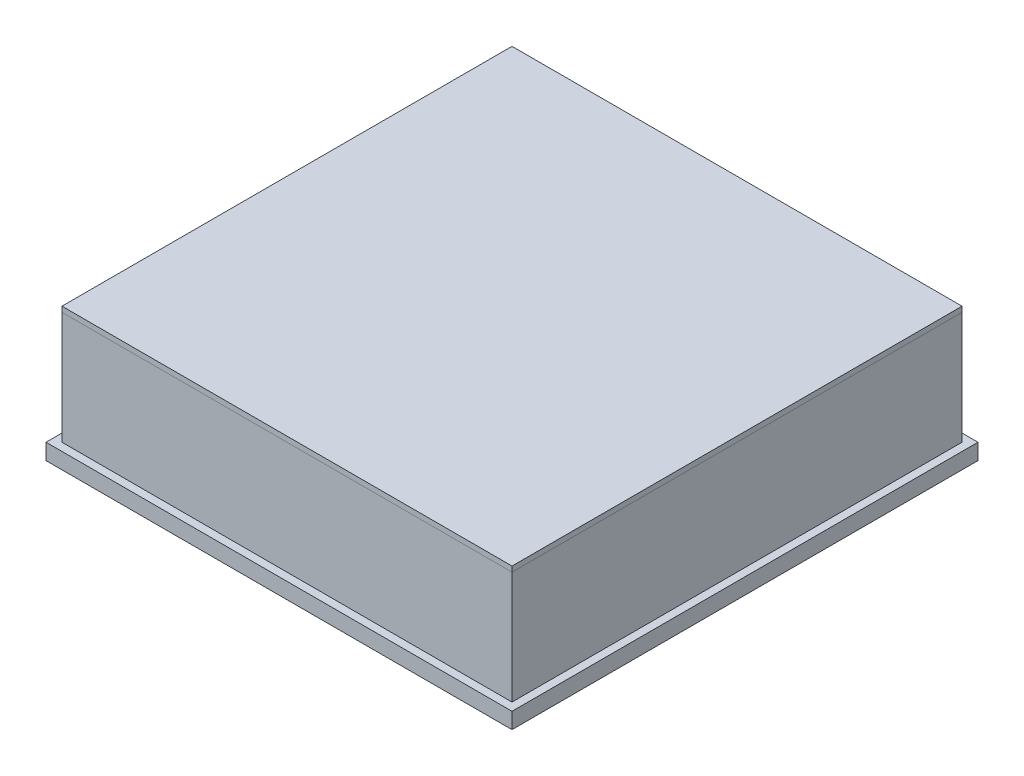
SolidWorks part; units mm, degrees
ref_plane "Front Plane" through (0, 0, 0) normal (0, 0, 1) x (1, 0, 0)
ref_plane "Top Plane" through (0, 0, 0) normal (0, 1, 0) x (1, 0, 0)
ref_plane "Right Plane" through (0, 0, 0) normal (1, 0, 0) x (0, 0, -1)
sketch "Sketch2" plane through (0, 0, 0) normal (0, 1, 0) x (1, 0, 0)
  line L0 (-4304.792, -4304.792) -> (-4304.792, 4304.792)
  line L1 (3999.992, -3999.992) -> (-3999.992, -3999.992)
  line L2 (3999.992, -3999.992) -> (3999.992, 3999.992)
  line L3 (3999.992, 3999.992) -> (-3999.992, 3999.992)
  line L4 (-3999.992, -3999.992) -> (-3999.992, 3999.992)
  line L5 (3999.992, -3999.992) -> (-3999.992, 3999.992) construction
  line L6 (3999.992, 3999.992) -> (-3999.992, -3999.992) construction
  line L7 (4304.792, 4304.792) -> (-4304.792, 4304.792)
  line L8 (4304.792, -4304.792) -> (4304.792, 4304.792)
  line L9 (4304.792, -4304.792) -> (-4304.792, -4304.792)
  point P0 (0, 0)
  dimension "D1" = 7999.984
  dimension "D2" = 7999.984
  dimension "D3" = 304.8
extrude "Boss-Extrude1" add sketch "Sketch2" along normal blind 1999.996
sketch "Sketch3" plane through (0, 0, 0) normal (0, -1, 0) x (1, 0, 0)
  line L0 (-4304.792, -4304.792) -> (-4304.792, 4304.792) construction
  line L1 (-4304.792, -4304.792) -> (-4304.792, 4304.792)
  line L2 (4304.792, -4304.792) -> (-4304.792, -4304.792) construction
  line L3 (4304.792, 4304.792) -> (4304.792, -4304.792) construction
  line L4 (-4304.792, 4304.792) -> (4304.792, 4304.792) construction
  line L5 (4304.792, -4304.792) -> (-4304.792, -4304.792)
  line L6 (4304.792, 4304.792) -> (4304.792, -4304.792)
  line L7 (-4304.792, 4304.792) -> (4304.792, 4304.792)
extrude "Boss-Extrude2" add sketch "Sketch3" along normal blind 152.4
sketch "Sketch4" plane through (0, -152.4, 0) normal (0, -1, 0) x (1, 0, 0)
  line L30 (-4457.192, 4457.192) -> (-4457.192, -4457.192)
  line L31 (-4457.192, -4457.192) -> (4457.192, -4457.192)
  line L32 (4457.192, -4457.192) -> (4457.192, 4457.192)
  line L33 (4457.192, 4457.192) -> (-4457.192, 4457.192)
  line L34 (-4457.192, 4457.192) -> (-4457.192, -4457.192)
  line L35 (-4457.192, -4457.192) -> (4457.192, -4457.192)
  line L36 (4457.192, -4457.192) -> (4457.192, 4457.192)
  line L37 (4457.192, 4457.192) -> (-4457.192, 4457.192)
  line L43 (3847.592, 3847.592) -> (-3847.592, 3847.592)
  line L44 (-3847.592, 3847.592) -> (-3847.592, -3847.592)
  line L45 (-3847.592, -3847.592) -> (3847.592, -3847.592)
  line L46 (3847.592, -3847.592) -> (3847.592, 3847.592)
  line L47 (3847.592, 3847.592) -> (-3847.592, 3847.592)
  line L48 (-3847.592, 3847.592) -> (-3847.592, -3847.592)
  line L49 (-3847.592, -3847.592) -> (3847.592, -3847.592)
  line L50 (3847.592, -3847.592) -> (3847.592, 3847.592)
  dimension "D1" = 152.4
  dimension "D2" = 152.4
extrude "Boss-Extrude3" add sketch "Sketch4" along normal blind 304.8
sketch "Sketch6" plane through (0, 0, 0) normal (0, 1, 0) x (1, 0, 0)
  line L0 (0, 0) -> (-3999.992, 3999.992) construction
  line L6 (-3999.992, 1656.8509) -> (-1656.8509, 1656.8509) construction
  line L7 (-3999.992, 3999.992) -> (-3999.992, -3999.992) construction
  line L19 (-1656.8509, 1656.8509) -> (-1656.8509, 3999.992) construction
  line L20 (3999.992, 3999.992) -> (-3999.992, 3999.992) construction
  line L22 (-1656.8509, 1656.8509) -> (0, 0) construction
  line L24 (1809.2509, 1504.4509) -> (1809.2509, 1809.2509)
  line L25 (-1504.4509, 1809.2509) -> (-1809.2509, 1809.2509)
  line L29 (-1504.4509, 1809.2509) -> (-1504.4509, 1504.4509)
  line L30 (-1504.4509, 1504.4509) -> (-1809.2509, 1504.4509)
  line L31 (-1809.2509, 1809.2509) -> (-1809.2509, 1504.4509)
  line L32 (-1504.4509, 1809.2509) -> (-1809.2509, 1504.4509) construction
  line L33 (-1504.4509, 1504.4509) -> (-1809.2509, 1809.2509) construction
  line L34 (1809.2509, 1809.2509) -> (1504.4509, 1809.2509)
  line L35 (1504.4509, 1504.4509) -> (1504.4509, 1809.2509)
  line L36 (1809.2509, 1504.4509) -> (1504.4509, 1504.4509)
  line L37 (1504.4509, -1809.2509) -> (1809.2509, -1809.2509)
  line L38 (1809.2509, -1809.2509) -> (1809.2509, -1504.4509)
  line L39 (1504.4509, -1504.4509) -> (1809.2509, -1504.4509)
  line L40 (1504.4509, -1809.2509) -> (1504.4509, -1504.4509)
  line L41 (-1809.2509, -1504.4509) -> (-1809.2509, -1809.2509)
  line L42 (-1809.2509, -1809.2509) -> (-1504.4509, -1809.2509)
  line L43 (-1504.4509, -1504.4509) -> (-1504.4509, -1809.2509)
  line L44 (-1809.2509, -1504.4509) -> (-1504.4509, -1504.4509)
  point P30 (0, 0)
  dimension "D1" = 304.8
extrude "Boss-Extrude5" add sketch "Sketch6" along normal up to surface (1999.996 mm away) contours L25 L31 L30 L29 | L36 L24 L34 L35 | L40 L37 L38 L39 | L44 L41 L42 L43 region at (1656.8509, 0, -1656.8509) region at (-1656.8509, 0, -1656.8509) region at (1656.8509, 0, 1656.8509) region at (-1656.8509, 0, 1656.8509) up to face at (0, 1999.996, 0)
sketch "Sketch7" plane through (0, 1999.996, 0) normal (0, 1, 0) x (1, 0, 0)
  line L1 (4304.792, -4304.792) -> (-4304.792, -4304.792)
  line L2 (4304.792, -4304.792) -> (4304.792, 4304.792)
  line L3 (4304.792, 4304.792) -> (-4304.792, 4304.792)
  line L4 (-4304.792, -4304.792) -> (-4304.792, 4304.792)
  line L5 (4304.792, -4304.792) -> (-4304.792, 4304.792) construction
  line L6 (4304.792, 4304.792) -> (-4304.792, -4304.792) construction
  point P0 (0, 0)
extrude "Boss-Extrude6" add sketch "Sketch7" along normal blind 101.6 separate body
sketch "Sketch8" plane through (0, 0, -1504.4509) normal (0, 0, 1) x (1, 0, 0)
  line L0 (-3999.992, 1999.996) -> (-3999.992, 0) construction
  line L1 (3999.992, 1999.996) -> (-3999.992, 1999.996)
  line L2 (3999.992, 1999.996) -> (3999.992, 1753.1524)
  line L3 (3999.992, 1753.1524) -> (-3999.992, 1753.1524)
  line L4 (-3999.992, 1999.996) -> (-3999.992, 1753.1524)
  line L5 (3999.992, 1999.996) -> (-3999.992, 1753.1524) construction
  line L6 (3999.992, 1753.1524) -> (-3999.992, 1999.996) construction
  line L7 (3999.992, 1999.996) -> (-3999.992, 1999.996) construction
  line L8 (3999.992, 1999.996) -> (-3999.992, 1999.996)
  point P0 (0, 1876.5742)
ref_axis "Axis1" through (0, 0, 0) along (0, 1, 0)
sketch "Right Plane Rebar" plane through (0, 0, 0) normal (1, 0, 0) x (0, 0, -1)
  line L0 (4247.642, 2050.796) -> (4247.642, -406.4)
  line L1 (-4457.192, -457.2) -> (4457.192, -457.2) construction
  line L2 (4057.142, 2031.746) -> (4057.142, 38.1)
  line L3 (4234.942, 1301.496) -> (4234.942, 1911.096)
  line L4 (-4304.792, 1999.996) -> (-4304.792, -152.4)
  line L5 (-4304.792, -152.4) -> (4304.792, -152.4)
  line L6 (4304.792, -152.4) -> (4304.792, 1999.996)
  line L7 (4304.792, 1999.996) -> (-4304.792, 1999.996)
  line L8 (-4304.792, 1999.996) -> (-4304.792, -152.4)
  line L9 (-4304.792, -152.4) -> (4304.792, -152.4)
  line L10 (4304.792, -152.4) -> (4304.792, 1999.996)
  line L12 (4107.942, 2038.096) -> (3498.342, 2038.096)
  line L13 (4107.942, 2050.796) -> (-4107.942, 2050.796)
  line L14 (0, 1407.3378) -> (0, -1407.3378) construction
  line L15 (3942.842, -101.6) -> (-3942.842, -101.6)
  line L16 (3999.992, 1999.996) -> (-3999.992, 1999.996)
  line L17 (3999.992, 1999.996) -> (-3999.992, 1999.996)
  line L18 (-4304.792, 2101.596) -> (4304.792, 2101.596) construction
  line L19 (3999.992, 0) -> (3999.992, 1999.996)
  line L20 (-3999.992, 0) -> (3999.992, 0)
  line L21 (-3999.992, 1999.996) -> (-3999.992, 0)
  line L27 (3999.992, 0) -> (3999.992, 1999.996)
  line L28 (-3999.992, 0) -> (3999.992, 0)
  line L29 (-3999.992, 1999.996) -> (-3999.992, 0)
  line L32 (4069.842, 647.7) -> (4069.842, 38.1)
  line L33 (3942.842, -88.9) -> (3333.242, -88.9)
  line L38 (4304.792, 1999.996) -> (-4304.792, 1999.996)
  arc A0 (4234.942, 1911.096) -> (4107.942, 2038.096) centre (4107.942, 1911.096) ccw
  arc A1 (3942.842, -88.9) -> (4069.842, 38.1) centre (3942.842, 38.1) ccw
  point P23 (4234.942, 2038.096)
  point P30 (0, 2050.796)
  point P41 (0, -101.6)
  dimension "D12" = 127
  dimension "D19" = 127
  dimension "D5" = 57.15
  dimension "Vertical Rebar Outer" = 2457.196
  dimension "D4" = 50.8
  dimension "D8" = 57.15
  dimension "D11" = 12.7
  dimension "D10" = 6.35
  dimension "D13" = 609.6
  dimension "D14" = 609.6
  dimension "D15" = 12.7
  dimension "D16" = 50.8
  dimension "D17" = 12.7
  dimension "D18" = 12.7
  dimension "D7" = 609.6
  dimension "D20" = 609.6
  dimension "Vertical Rebar Inner" = 1993.646
  dimension "Lid Rebar Length" = 8215.884
  dimension "Base Rebar Length" = 7885.684
  dimension "D3" = 50.8
  dimension "D6" = 50.8
sketch "Front Plane Rebar" plane through (0, 0, 0) normal (0, 0, 1) x (1, 0, 0)
  line L0 (4247.642, 2050.796) -> (4247.642, -406.4)
  line L1 (3999.992, 1999.996) -> (3999.992, 0) construction
  line L2 (4057.142, 2019.046) -> (4057.142, 50.8)
  line L3 (4234.942, 1288.796) -> (4234.942, 1898.396)
  line L4 (-4304.792, 2101.596) -> (4304.792, 2101.596) construction
  line L5 (4457.192, -457.2) -> (-4457.192, -457.2) construction
  line L6 (4457.192, -152.4) -> (-4457.192, -152.4) construction
  line L7 (4304.792, 2101.596) -> (-4304.792, 2101.596) construction
  line L8 (-4304.792, 1999.996) -> (-4304.792, -152.4)
  line L9 (-4304.792, -152.4) -> (4304.792, -152.4)
  line L10 (4304.792, -152.4) -> (4304.792, 1999.996)
  line L12 (4107.942, 2025.396) -> (3498.342, 2025.396)
  line L13 (4107.942, 2038.096) -> (-4107.942, 2038.096)
  line L15 (3942.842, -88.9) -> (-3942.842, -88.9)
  line L17 (3999.992, 1999.996) -> (-3999.992, 1999.996)
  line L19 (-3999.992, 0) -> (3999.992, 0)
  line L20 (3999.992, 0) -> (3999.992, 1999.996)
  line L21 (3999.992, 1999.996) -> (-3999.992, 1999.996)
  line L22 (-3999.992, 1999.996) -> (-3999.992, 0)
  line L23 (-3999.992, 0) -> (3999.992, 0)
  line L27 (3999.992, 0) -> (3999.992, 1999.996)
  line L28 (-3999.992, 0) -> (3999.992, 0)
  line L29 (-3999.992, 1999.996) -> (-3999.992, 0)
  line L32 (4069.842, 660.4) -> (4069.842, 50.8)
  line L33 (3942.842, -76.2) -> (3333.242, -76.2)
  line L34 (3999.992, 0) -> (3999.992, 1999.996)
  line L35 (3999.992, 1999.996) -> (-3999.992, 1999.996)
  line L36 (-3999.992, 1999.996) -> (-3999.992, 0)
  line L37 (4304.792, -152.4) -> (4304.792, 1999.996)
  line L38 (4304.792, 1999.996) -> (-4304.792, 1999.996)
  line L39 (-4304.792, -152.4) -> (4304.792, -152.4)
  line L40 (-4304.792, 1999.996) -> (-4304.792, -152.4)
  line L41 (4304.792, 1999.996) -> (-4304.792, 1999.996)
  line L42 (4304.792, -152.4) -> (4304.792, 1999.996)
  line L43 (-4304.792, -152.4) -> (4304.792, -152.4)
  line L44 (-4304.792, 1999.996) -> (-4304.792, -152.4)
  line L45 (4304.792, 1999.996) -> (-4304.792, 1999.996)
  arc A0 (4234.942, 1898.396) -> (4107.942, 2025.396) centre (4107.942, 1898.396) ccw
  arc A1 (3942.842, -76.2) -> (4069.842, 50.8) centre (3942.842, 50.8) ccw
  point P23 (4234.942, 2025.396)
  point P30 (0, 2038.096)
  point P41 (0, -88.9)
  dimension "D12" = 127
  dimension "D19" = 127
  dimension "Vertical Rebar Outer" = 2457.196
  dimension "D4" = 50.8
  dimension "D11" = 12.7
  dimension "D10" = 6.35
  dimension "D13" = 609.6
  dimension "D14" = 609.6
  dimension "D15" = 12.7
  dimension "D17" = 12.7
  dimension "D18" = 12.7
  dimension "D7" = 609.6
  dimension "D20" = 609.6
  dimension "Lid Rebar Length" = 8215.884
  dimension "Base Rebar Length" = 7885.684
  dimension "D5" = 57.15
  dimension "D8" = 57.15
  dimension "D16" = 63.5
  dimension "Vertical Rebar Inner" = 1968.246
  dimension "D3" = 63.5
  dimension "D21" = 50.8
sketch "Sketch9" plane through (0, -152.4, 0) normal (0, 1, 0) x (1, 0, 0)
  line L0 (-4260.342, 4406.392) -> (-4260.342, -4406.392)
  line L1 (-4457.192, -4457.192) -> (-4457.192, 4457.192) construction
  line L2 (-4457.192, -4457.192) -> (-4457.192, 4457.192)
  line L3 (-3847.592, -3847.592) -> (-3847.592, 3847.592) construction
  line L4 (-3847.592, -3847.592) -> (-3847.592, 3847.592)
  line L5 (-4457.192, 4457.192) -> (4457.192, 4457.192) construction
  line L6 (4457.192, -4457.192) -> (-4457.192, -4457.192) construction
  line L7 (-4044.442, 4152.392) -> (-4044.442, -4152.392)
  line L8 (4406.392, 4260.342) -> (-4406.392, 4260.342)
  line L9 (4152.392, 4044.442) -> (-4152.392, 4044.442)
  line L10 (4260.342, -4406.392) -> (4260.342, 4406.392)
  line L11 (4044.442, -4152.392) -> (4044.442, 4152.392)
  line L12 (-4406.392, -4260.342) -> (4406.392, -4260.342)
  line L13 (-4152.392, -4044.442) -> (4152.392, -4044.442)
  point P27 (0, 0)
  dimension "D3" = 50.8
  dimension "D1" = 196.85
  dimension "D2" = 50.8
  dimension "D4" = 196.85
  dimension "D5" = 304.8
  dimension "D6" = 304.8
  dimension "D7" = 8812.784
  dimension "D8" = 8304.784
  dimension "D9" = 4
sketch "Sketch11" plane through (0, 0, -1504.4509) normal (0, 0, 1) x (1, 0, 0)
  line L0 (-1758.4509, 2050.796) -> (-1758.4509, -406.4)
  line L2 (-4304.792, 2101.596) -> (4304.792, 2101.596) construction
  line L3 (4457.192, -457.2) -> (-4457.192, -457.2) construction
  line L6 (-1504.4509, 0) -> (-1504.4509, 1999.996)
  line L7 (-1504.4509, 1999.996) -> (-1809.2509, 1999.996)
  line L8 (-1809.2509, 1999.996) -> (-1809.2509, 0)
  line L9 (-1809.2509, 0) -> (-1504.4509, 0)
  line L10 (-1504.4509, 0) -> (-1504.4509, 1999.996)
  line L11 (-1504.4509, 1999.996) -> (-1809.2509, 1999.996)
  line L12 (-1809.2509, 1999.996) -> (-1809.2509, 0)
  line L13 (-1809.2509, 0) -> (-1504.4509, 0)
  dimension "D4" = 50.8
  dimension "D3" = 50.8
  dimension "D2" = 50.8
equation "\"Rebar Diameter\"=0.5"
equation "\"Min Coverage\"=2"
equation "\"D5@Right Plane Rebar\" = \"Rebar Diameter\" / 2 + \"Min Coverage\""
equation "\"D4@Right Plane Rebar\" = \"Min Coverage\""
equation "\"D8@Right Plane Rebar\" = \"Min Coverage\" + \"Rebar Diameter\" / 2"
equation "\"Contact Length\"= 24"
equation "\"D11@Right Plane Rebar\" = \"Rebar Diameter\""
equation "\"Rebar Bend Radius\"= 5"
equation "\"D12@Right Plane Rebar\" = \"Rebar Bend Radius\""
equation "\"D10@Right Plane Rebar\" = \"Rebar Diameter\" / 2"
equation "\"D13@Right Plane Rebar\" = \"Contact Length\""
equation "\"D14@Right Plane Rebar\" = \"Contact Length\""
equation "\"D15@Right Plane Rebar\" = \"Rebar Diameter\""
equation "\"D16@Right Plane Rebar\" = \"Min Coverage\""
equation "\"D17@Right Plane Rebar\" = \"Rebar Diameter\""
equation "\"D18@Right Plane Rebar\" = \"Rebar Diameter\""
equation "\"D19@Right Plane Rebar\" = \"Rebar Bend Radius\""
equation "\"D7@Right Plane Rebar\" = \"Contact Length\""
equation "\"D20@Right Plane Rebar\" = \"Contact Length\""
equation "\"D3@Right Plane Rebar\" = \"Min Coverage\""
equation "\"D6@Right Plane Rebar\" = \"Min Coverage\""
equation "\"D3@Front Plane Rebar\" = \"Rebar Diameter\" + \"Min Coverage\""
equation "\"D4@Front Plane Rebar\" = \"Min Coverage\""
equation "\"D16@Front Plane Rebar\" = \"Min Coverage\" + \"Rebar Diameter\""
equation "\"D21@Front Plane Rebar\" = \"Min Coverage\""
equation "\"D1@Sketch9\"=7.75"
equation "\"D2@Sketch9\"=\"Min Coverage\""
equation "\"D3@Sketch9\"=\"Min Coverage\""
equation "\"D4@Sketch9\"=7.75"
equation "\"D3@Sketch11\"=\"Min Coverage\""
equation "\"D4@Sketch11\"=\"Min Coverage\""
equation "\"D2@Sketch11\"=\"Min Coverage\""
